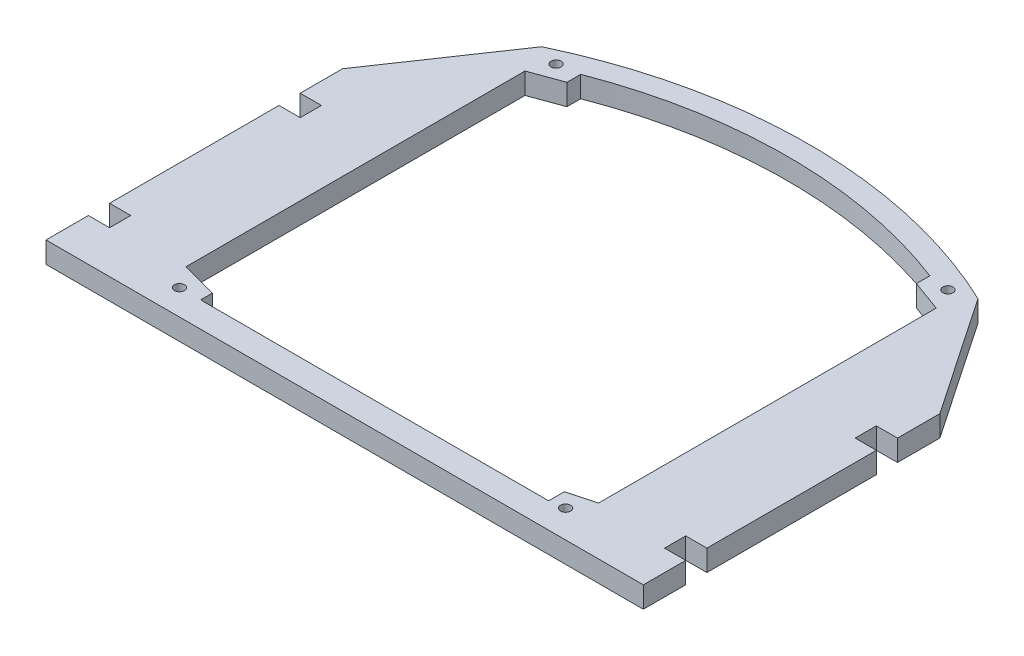
SolidWorks part; units mm, degrees
ref_plane "Front Plane" through (0, 0, 0) normal (0, 0, 1) x (1, 0, 0)
ref_plane "Top Plane" through (0, 0, 0) normal (0, 1, 0) x (1, 0, 0)
ref_plane "Right Plane" through (0, 0, 0) normal (1, 0, 0) x (0, 0, -1)
sketch "Sketch1" plane through (0, 0, 0) normal (0, 1, 0) x (1, 0, 0)
  line L0 (-70.5, -58) -> (-70.5, 12)
  line L1 (70.5, -58) -> (70.5, 12)
  line L2 (-48.5, -46.9211) -> (-48.5, 33.0744)
  line L3 (48.5, 33.138) -> (48.5, -46.5952)
  line L4 (70.5, -58) -> (-70.5, -58)
  line L5 (-40, -52) -> (42.15, -52)
  line L6 (-70.5, 12) -> (-51.5, 40)
  line L9 (70.5, 12) -> (51.5, 40)
  line L10 (-48.5, -46.9211) -> (-40, -49.1986)
  line L11 (-50, 43) -> (50, 43) construction
  line L12 (-50, 43) -> (-50, -57) construction
  line L13 (-50, -57) -> (50, -57) construction
  line L14 (50, 43) -> (50, -57) construction
  line L15 (-40, -49.1986) -> (-40, -52)
  line L16 (42.15, -52) -> (42.15, -48.2967)
  line L17 (42.15, -48.2967) -> (48.5, -46.5952)
  line L18 (41.15, 38.9986) -> (41.15, 35.8131)
  line L19 (41.15, 35.8131) -> (48.5, 33.138)
  line L20 (-48.5, 33.0744) -> (-41.25, 35.7131)
  line L21 (-41.25, 35.7131) -> (-41.25, 38.9602)
  arc A0 (-51.5, 40) -> (51.5, 40) centre (0, -68.387) cw
  arc A2 (-41.25, 38.9602) -> (41.15, 38.9986) centre (0, -68.387) cw
  circle A4 centre (-46.25, 38.15) radius 1.2
  circle A5 centre (46.15, 38.25) radius 1.2
  circle A6 centre (45.65, -51.5) radius 1.2
  circle A7 centre (-45, -52) radius 1.2
  dimension "D1" = 120
  dimension "D11" = 52
  dimension "D7" = 6
  dimension "D9" = 2.4
  dimension "D36" = 5
  dimension "D2" = 141
  dimension "D3" = 70.5
  dimension "D5" = 48.5
  dimension "D6" = 100
  dimension "D4" = 97
  dimension "D8" = 50
  dimension "D10" = 5
  dimension "D12" = 5
  dimension "D13" = 3.75
  dimension "D14" = 4.85
  dimension "D15" = 3.85
  dimension "D16" = 4.75
  dimension "D17" = 5.5
  dimension "D18" = 4.35
  dimension "D20" = 4
  dimension "D21" = 5
  dimension "D22" = 105
  dimension "D23" = 3.5
  dimension "D24" = 4
  dimension "D25" = 105
  dimension "D26" = 4
  dimension "D27" = 5
  dimension "D28" = 110
  dimension "D29" = 5
  dimension "D30" = 4
  dimension "D31" = 110
  dimension "D32" = 57
  dimension "D33" = 70
  dimension "D34" = 3
  dimension "D35" = 3
  dimension "D37" = 40
extrude "Boss-Extrude1" add sketch "Sketch1" along normal blind 5
sketch "Sketch2" plane through (0, 5, 0) normal (0, 1, 0) x (1, 0, 0)
  line L0 (-70.5, 12) -> (-70.5, -58) construction
  line L1 (-70.5, -48) -> (-65.5, -48)
  line L2 (-70.5, -48) -> (-70.5, -43)
  line L3 (-70.5, -43) -> (-65.5, -43)
  line L4 (-65.5, -48) -> (-65.5, -43)
  line L5 (-70.5, -58) -> (70.5, -58) construction
  line L6 (-70.5, -3) -> (-65.5, -3)
  line L7 (-70.5, -3) -> (-70.5, 2)
  line L8 (-70.5, 2) -> (-65.5, 2)
  line L9 (-65.5, -3) -> (-65.5, 2)
  dimension "D1" = 5
  dimension "D2" = 40
  dimension "D3" = 10
extrude "Cut-Extrude1" cut sketch "Sketch2" against normal up to next
mirror "Mirror1" about plane through (0, 0, 0) normal (1, 0, 0) of "Cut-Extrude1"
